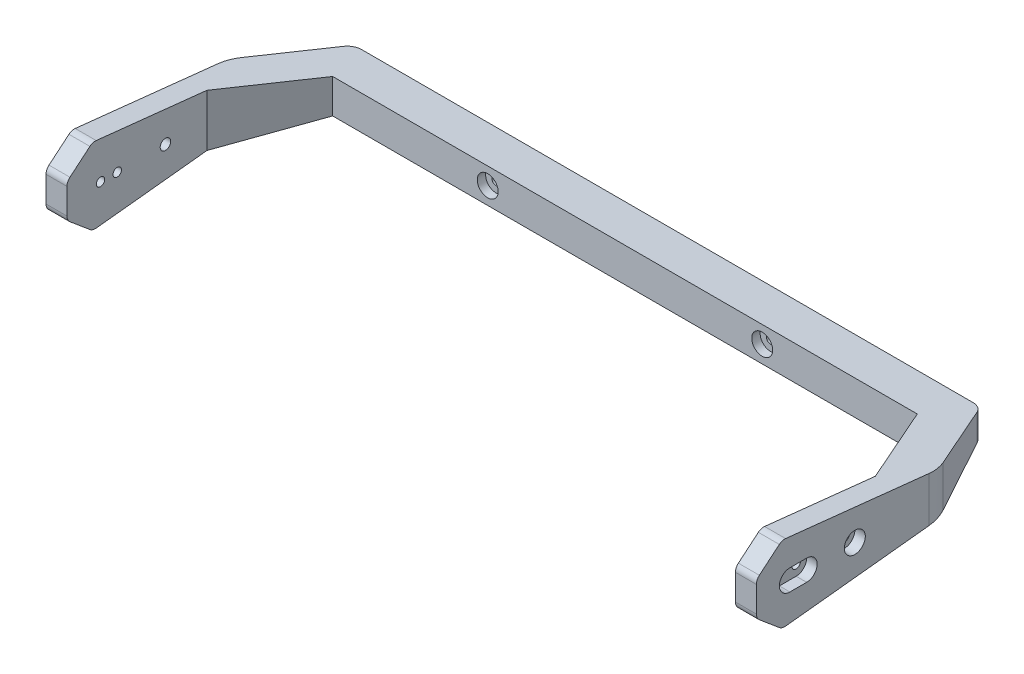
SolidWorks part; units mm, degrees
ref_plane "Front Plane" through (0, 0, 0) normal (0, 0, 1) x (1, 0, 0)
ref_plane "Top Plane" through (0, 0, 0) normal (0, 1, 0) x (1, 0, 0)
ref_plane "Right Plane" through (0, 0, 0) normal (1, 0, 0) x (0, 0, -1)
ref_plane "Plane1" through (79.75, 0, 0) normal (1, 0, 0) x (0, 0, -1)
ref_plane "Plane2" through (-79.75, 0, 0) normal (1, 0, 0) x (0, 0, -1)
sketch "Sketch4" plane through (79.75, 0, 0) normal (1, 0, 0) x (0, 0, -1)
  line L2 (0, 0) -> (4, 0) construction
  line L3 (4, 0) -> (15.5, 0) construction
  line L4 (-8, 4) -> (-8, -4)
  line L5 (-8, -4) -> (-1.8716, -9.1423)
  line L6 (-1.8716, -9.1423) -> (55.5, -3)
  line L7 (55.5, -3) -> (55.5, 3)
  line L8 (55.5, 3) -> (-1.8716, 9.1423)
  line L9 (-1.8716, 9.1423) -> (-8, 4)
  circle A2 centre (0, 0) radius 1
  circle A3 centre (4, 0) radius 1
  circle A4 centre (15.5, 0) radius 1.25
  point P1 (-8, 0)
  point P3 (55.5, 0)
  dimension "D1" = 11.5
  dimension "D3" = 2.5
  dimension "D4" = 2
  dimension "D5" = 2
  dimension "D6" = 40
  dimension "D7" = 8
  dimension "D2" = 4
  dimension "D8" = 130
  dimension "D9" = 130
  dimension "D10" = 6
  dimension "D11" = 8
  dimension "D12" = 8
extrude "Boss-Extrude1" add sketch "Sketch4" along normal blind 5
mirror "Mirror1" about plane through (0, 0, 0) normal (1, 0, 0) of bodies 101
sketch "Sketch5" plane through (0, 0, 0) normal (1, 0, 0) x (0, 0, -1)
  line L3 (51.5, 3.4282) -> (51.5, -3.4282)
  line L8 (55.5, 3) -> (-1.8716, 9.1423) construction
  line L9 (55.5, -3) -> (55.5, 3) construction
  line L10 (-1.8716, -9.1423) -> (55.5, -3) construction
  line L11 (51.5, 3.4282) -> (55.5, 3)
  line L12 (55.5, 3) -> (55.5, -3)
  line L13 (55.5, -3) -> (51.5, -3.4282)
  line L14 (45.4, 4.0813) -> (45.4, -4.0813)
  line L15 (45.4, -4.0813) -> (49.4, -3.6531)
  line L16 (49.4, -3.6531) -> (49.4, 3.6531)
  line L17 (49.4, 3.6531) -> (45.4, 4.0813)
  point P21 (55.5, 0)
  dimension "D3" = 4
  dimension "D1" = 4
  dimension "D2" = 2.1
extrude "Boss-Extrude2" add sketch "Sketch5" along normal up to surface (79.75 mm away) and the other way up to surface (79.75 mm away) up to face at (79.75, 0, -15.2095) other way up to face at (-79.75, 0, -15.2095)
sketch "Sketch6" plane through (0, 0, 0) normal (0, 1, 0) x (1, 0, 0)
  line L0 (-79.75, 51.5) -> (-65.5, 51.5)
  line L1 (-79.75, -9.9) -> (-79.75, 9.9) construction
  line L4 (-65.5, 51.5) -> (-65.5, 49.4)
  line L6 (-65.5, 49.4) -> (-79.75, 49.4)
  line L7 (-79.75, 49.4) -> (-79.75, 51.5)
  line L8 (-65.5, 49.4) -> (65.5, 49.4) construction
  line L9 (65.5, 49.4) -> (79.75, 49.4)
  line L10 (79.75, -9.9) -> (79.75, 9.9) construction
  line L11 (79.75, 49.4) -> (79.75, 51.5)
  line L12 (79.75, 51.5) -> (65.5, 51.5)
  line L13 (65.5, 51.5) -> (65.5, 49.4)
  line L14 (0, 49.4) -> (0, 0) construction
  line L15 (79.75, 51.5) -> (-79.75, 51.5) construction
  line L16 (79.75, 49.4) -> (-79.75, 49.4) construction
  dimension "D1" = 131
extrude "Boss-Extrude3" add sketch "Sketch6" along normal up to surface and the other way up to surface up to face at (0, 3.5407, -50.45) other way up to face at (0, -6.3415, -24.2892)
sketch "Sketch11" plane through (0, 0, -45.4) normal (0, 0, 1) x (1, 0, 0)
  line L0 (0, 0) -> (-32.75, 0) construction
  line L1 (-32.75, 0) -> (-65.5, 0) construction
  line L2 (0, 0) -> (32.75, 0) construction
  line L3 (32.75, 0) -> (65.5, 0) construction
  circle A0 centre (-32.75, 0) radius 1
  circle A1 centre (32.75, 0) radius 1
  dimension "D1" = 2
  dimension "D2" = 131
extrude "Cut-Extrude4" cut sketch "Sketch11" against normal through all
sketch "Sketch12" plane through (0, 0, -45.4) normal (0, 0, 1) x (1, 0, 0)
  circle A0 centre (-32.75, 0) radius 2.5
  circle A1 centre (32.75, 0) radius 2.5
  circle A2 centre (32.75, 0) radius 1 construction
  circle A3 centre (-32.75, 0) radius 1 construction
  dimension "D1" = 5
extrude "Cut-Extrude5" cut sketch "Sketch12" against normal blind 2
sketch "Sketch13" plane through (0, 0, -55.5) normal (0, 0, -1) x (-1, 0, 0)
  circle A0 centre (-32.75, 0) radius 2.5
  circle A1 centre (32.75, 0) radius 2.5
  circle A2 centre (32.75, 0) radius 1 construction
  circle A3 centre (-32.75, 0) radius 1 construction
  dimension "D1" = 5
extrude "Cut-Extrude6" cut sketch "Sketch13" against normal blind 2
chamfer "Chamfer3" distance 10 distance2 20 2 edges at (79.75, 0, -45.4) (84.75, 0, -55.5) first distance on face at (-30.25, 0, -45.4) first distance on face at (30.25, 0, -55.5)
chamfer "Chamfer4" distance 20 distance2 10 2 edges at (-79.75, 0, -45.4) (-84.75, 0, -55.5) first distance on face at (-79.75, 0, -11.8428) first distance on face at (-84.75, 0, -5)
ref_plane "Plane3" through (0, 2.5, 0) normal (0, 1, 0) x (1, 0, 0)
sketch "Sketch14" plane through (0, 2.5, 0) normal (0, 1, 0) x (1, 0, 0)
  line L0 (65.5, 51.5) -> (65.5, 49.4)
  line L1 (65.5, 49.4) -> (-65.5, 49.4)
  line L2 (-65.5, 49.4) -> (-65.5, 51.5)
  line L3 (-65.5, 51.5) -> (65.5, 51.5)
extrude "Boss-Extrude4" add sketch "Sketch14" along normal up to surface (0.9282 mm away) up to face at (0, 3.5407, -50.45)
sketch "Sketch15" plane through (84.75, 0, 0) normal (1, 0, 0) x (0, 0, -1)
  line L0 (4, 2.5) -> (0, 2.5)
  line L1 (0, -2.5) -> (4, -2.5)
  circle A0 centre (15.5, 0) radius 2.5
  arc A1 (4, -2.5) -> (4, 2.5) centre (4, 0) ccw
  arc A2 (0, 2.5) -> (0, -2.5) centre (0, 0) ccw
  circle A3 centre (0, 0) radius 1 construction
  circle A4 centre (4, 0) radius 1 construction
  circle A5 centre (15.5, 0) radius 1.25 construction
  dimension "D1" = 5
extrude "Cut-Extrude7" cut sketch "Sketch15" against normal blind 2.5
mirror "Mirror2" about plane through (0, 0, 0) normal (1, 0, 0) of "Cut-Extrude7"
fillet "Fillet1" radius 2 8 edges at (-82.25, -9.1423, 1.8716) (-82.25, -4, 8) (-82.25, 4, 8) (-82.25, 9.1423, 1.8716) (82.25, -9.1423, 1.8716) (82.25, -4, 8) (82.25, 4, 8) (82.25, 9.1423, 1.8716)
fillet "Fillet2" radius 10 2 edges at (84.75, 0, -35.5) (-84.75, 0, -35.5)
fillet "Fillet3" radius 3 2 edges at (-74.75, 0, -55.5) (74.75, 0, -55.5)
